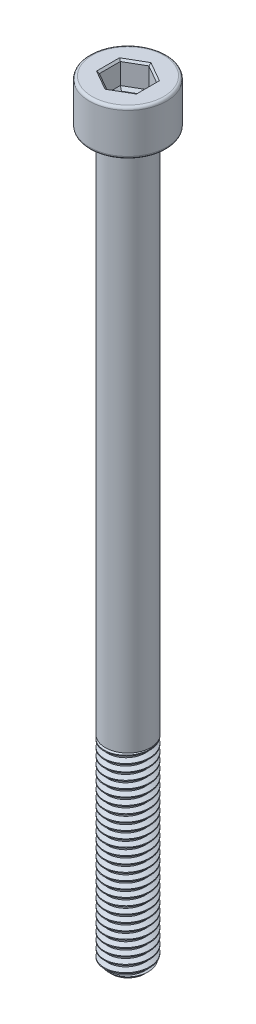
SolidWorks part; units mm, degrees
material "AISI Type A2 Tool Steel"
ref_plane "Front Plane" through (0, 0, 0) normal (0, 0, 1) x (1, 0, 0)
ref_plane "Top Plane" through (0, 0, 0) normal (0, 1, 0) x (1, 0, 0)
ref_plane "Right Plane" through (0, 0, 0) normal (1, 0, 0) x (0, 0, -1)
sketch "Sketch1" plane through (0, 0, 0) normal (0, 1, 0) x (1, 0, 0)
  circle A0 centre (0, 0) radius 2.5
  dimension "D1" = 5
extrude "Boss-Extrude1" add sketch "Sketch1" along normal blind 22
thread "Thread1" pitch 0.8 method cut profile "Thread Profile1" start angle 0, offset 1, length 0, pitch 0.8, diameter 5
ref_plane "Plane1" through (-2.5, 23, 0) normal (0, 0, 1) x (-1, 0, 0)
sketch "Thread Profile1" plane through (-2.5, 23, 0) normal (0, 0, 1) x (-1, 0, 0)
  line L0 (0, 0) -> (0, 0.8) construction
  line L11 (0, 0) -> (0, 0.7)
  line L12 (0, 0.7) -> (-0.433, 0.45)
  line L13 (-0.433, 0.45) -> (-0.433, 0.25)
  line L15 (-0.433, 0.25) -> (0, 0)
  line L17 (-0.433, 0.35) -> (0, 0.35) construction
  point P2 (0, 0)
  dimension "Pitch" = 0.8
  dimension "Profile_Angle" = 60
  dimension "Profile_Land" = 0.2
  dimension "Profile_Height" = 0.433
sketch "Sketch2" plane through (0, 22, 0) normal (0, 1, 0) x (1, 0, 0)
  circle A0 centre (0, 0) radius 2.5
  dimension "D1" = 5
extrude "Boss-Extrude2" add sketch "Sketch2" along normal blind 58
sketch "Sketch3" plane through (0, 80, 0) normal (0, 1, 0) x (1, 0, 0)
  circle A0 centre (0, 0) radius 4.25
  dimension "D1" = 8.5
extrude "Boss-Extrude3" add sketch "Sketch3" along normal blind 5
fillet "Fillet1" radius 0.3 2 edges at (0, 80, 4.25) (0, 85, 4.25)
sketch "Sketch4" plane through (0, 0, 0) normal (0, 0, 1) x (1, 0, 0)
  line L0 (0, 0) -> (0, 0.4416) construction
  line L1 (0, 0) -> (2.51, 0) construction
  line L2 (2.51, 0) -> (2.51, 0.7)
  line L3 (2.51, 0.7) -> (1.81, 0)
  line L4 (1.81, 0) -> (2.51, 0)
  dimension "D1" = 0.7
  dimension "D2" = 45
  dimension "D3" = 2.51
revolve "Cut-Revolve1" cut sketch "Sketch4" angle 360 about L0
sketch "Sketch5" plane through (0, 85, 0) normal (0, 1, 0) x (1, 0, 0)
  line L1 (0, 2.3094) -> (-2, 1.1547)
  line L2 (-2, 1.1547) -> (-2, -1.1547)
  line L3 (-2, -1.1547) -> (0, -2.3094)
  line L4 (0, -2.3094) -> (2, -1.1547)
  line L5 (2, -1.1547) -> (2, 1.1547)
  line L6 (2, 1.1547) -> (0, 2.3094)
  circle A0 centre (0, 0) radius 2 construction
  dimension "D1" = 4
extrude "Cut-Extrude1" cut sketch "Sketch5" against normal blind 2.5
chamfer "Chamfer1" distance 0.2 angle 45 6 edges at (-1, 85, 1.7321) (1, 85, 1.7321) (2, 85, 0) (1, 85, -1.7321) (-1, 85, -1.7321) (-2, 85, 0)
sketch "Sketch6" plane through (0, 82.5, 0) normal (0, 1, 0) x (1, 0, 0)
  line L1 (0, 2.3094) -> (-2, 1.1547)
  line L2 (-2, 1.1547) -> (-2, -1.1547)
  line L3 (-2, -1.1547) -> (0, -2.3094)
  line L4 (0, -2.3094) -> (2, -1.1547)
  line L5 (2, -1.1547) -> (2, 1.1547)
  line L6 (2, 1.1547) -> (0, 2.3094)
  circle A0 centre (0, 0) radius 2 construction
extrude "Cut-Extrude2" cut sketch "Sketch6" against normal blind 0.3 draft 45
